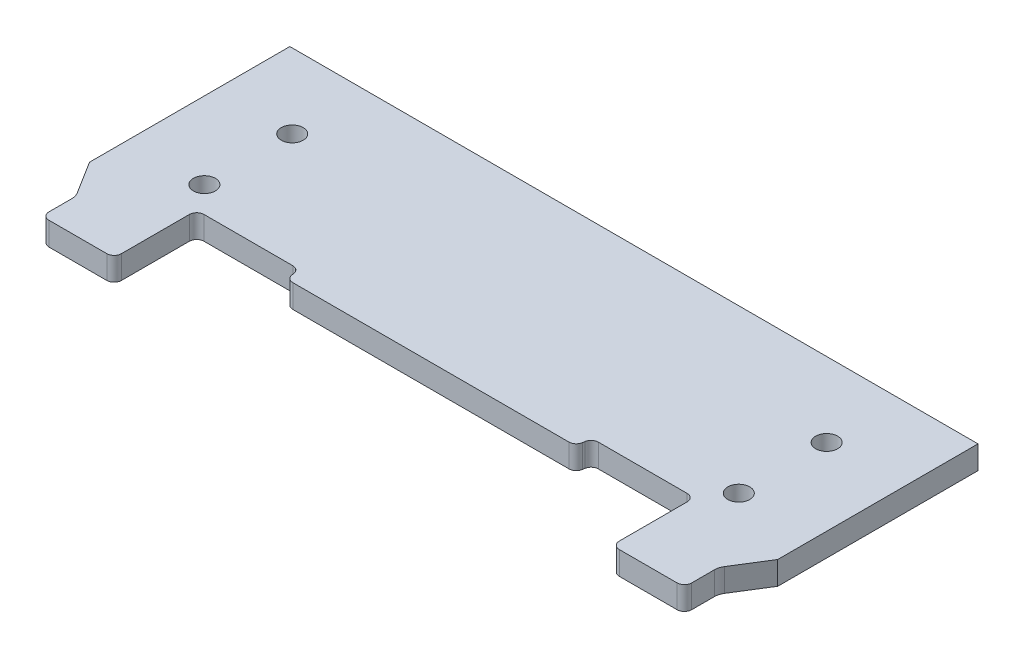
SolidWorks part; units mm, degrees
note: '?' marks a value the reader was unsure of.
material "6061 Alloy"
ref_plane "Front Plane" through (0, 0, 0) normal (0, 0, 1) x (1, 0, 0)
ref_plane "Top Plane" through (0, 0, 0) normal (0, 1, 0) x (1, 0, 0)
ref_plane "Right Plane" through (0, 0, 0) normal (1, 0, 0) x (0, 0, -1)
sketch "Sketch1" plane through (0, 0, 0) normal (0, 1, 0) x (1, 0, 0)
  line L0 (0, 0) -> (0, -55.55) construction
  line L1 (-83.4462, -16.178) -> (-71.2857, -8.5793) construction
  line L6 (0, 0) -> (-59.046, 61.1439) construction
  line L7 (0, 0) -> (-72.0841, -45.0431) construction
  line L8 (-33.174, 78.2591) -> (-23.2129, 67.9442) construction
  line L9 (-72.0841, -45.0431) -> (-70.388, -43.9833) construction
  line L10 (-70.388, -43.9833) -> (-84.9608, -20.662) construction
  line L11 (-84.9608, -20.662) -> (-72.2401, -12.7132) construction
  line L12 (-72.2401, -12.7132) -> (-43.0945, -59.3558) construction
  line L13 (-43.0945, -59.3558) -> (-55.8152, -67.3046) construction
  line L14 (-55.8152, -67.3046) -> (-70.388, -43.9833) construction
  line L21 (-59.046, 61.1439) -> (-57.6566, 59.7052)
  line L22 (-77.4385, 40.6021) -> (-37.8748, 78.8083) construction
  line L23 (-73.9694, 32.6911) -> (-77.0537, 35.885)
  line L24 (-37.8748, 78.8083) -> (-27.4549, 68.0182) construction
  line L25 (-27.4549, 68.0182) -> (-67.0186, 29.812) construction
  line L26 (-67.0186, 29.812) -> (-77.4385, 40.6021) construction
  line L27 (-43.0945, -64.8266) -> (-34, -64.8266)
  line L33 (-86.5505, -18.1178) -> (-71.2857, -8.5793) construction
  line L34 (0, 0) -> (0, 50000) construction
  line L35 (0, 0) -> (-50000, 0) construction
  line L36 (-64.3366, -55.55) -> (-19.7189, -55.55) construction
  line L38 (-67.0927, 25.57) -> (-79.5965, 38.5181) construction
  line L39 (-54.9774, -64.8266) -> (0, -64.8266) construction
  line L40 (-35.7168, 80.8923) -> (-23.2129, 67.9442) construction
  line L41 (-38.9606, -60.3102) -> (-54.2255, -69.8488) construction
  line L42 (-34, -55.55) -> (-19.7189, -55.55) construction
  line L43 (-43.0945, -64.8266) -> (-43.0945, -58.4123) construction
  line L45 (73.9694, 32.6911) -> (77.0537, 35.885)
  line L46 (-71.2857, -8.5793) -> (-38.9606, -60.3102) construction
  line L47 (83.4462, -16.178) -> (79.6809, -13.8252)
  line L48 (69.4846, -16.1792) -> (43.8945, -57.132)
  line L50 (43.0945, -64.8266) -> (34, -64.8266)
  line L51 (34, -55.55) -> (34, -64.8266)
  line L52 (0, 0) -> (72.0841, -45.0431) construction
  line L53 (0, 0) -> (59.046, 61.1439) construction
  line L54 (-30.0897, 75.0653) -> (-30.2847, 63.8954)
  line L55 (-62.7996, 32.4961) -> (-30.2847, 63.8954)
  line L56 (-30.0897, 75.0653) -> (-33.174, 78.2591)
  line L57 (73.9694, 32.6911) -> (77.0537, 35.885)
  line L58 (30.0897, 75.0653) -> (33.174, 78.2591)
  line L59 (-34, -55.55) -> (-34, -53.55)
  line L60 (62.7996, 32.4961) -> (30.2847, 63.8954)
  line L61 (-73.9694, 32.6911) -> (-62.7996, 32.4961)
  line L62 (-77.0537, 35.885) -> (-67.0927, 25.57) construction
  line L63 (-83.4462, -16.178) -> (-79.6809, -13.8252)
  line L64 (-79.6809, -13.8252) -> (-69.4846, -16.1792)
  line L65 (-69.4846, -16.1792) -> (-43.8945, -57.132)
  line L66 (-27.4549, 68.0182) -> (-23.2129, 67.9442) construction
  line L67 (-72.2401, -12.7132) -> (-71.2857, -8.5793) construction
  line L68 (30.0897, 75.0653) -> (30.2847, 63.8954)
  line L69 (73.9694, 32.6911) -> (62.7996, 32.4961)
  line L70 (-34, -55.55) -> (-34, -64.8266)
  line L71 (79.6809, -13.8252) -> (69.4846, -16.1792)
  line L72 (-34, -53.55) -> (-20, -53.55)
  line L73 (-20, -53.55) -> (-19.7189, -55.55)
  line L74 (-19.7189, -55.55) -> (19.7189, -55.55)
  line L75 (20, -53.55) -> (19.7189, -55.55)
  line L76 (34, -53.55) -> (20, -53.55)
  line L77 (34, -55.55) -> (34, -53.55)
  line L78 (-43.0945, -64.8266) -> (-43.8945, -64.8266)
  line L79 (-19.7189, -55.55) -> (0, -55.55) construction
  line L80 (-19.7189, -55.55) -> (34, -55.55) construction
  line L81 (-43.8945, -64.8266) -> (-43.8945, -57.132)
  line L82 (-43.0945, -58.4123) -> (-43.8945, -57.132) construction
  line L83 (43.8945, -64.8266) -> (43.8945, -57.132)
  line L84 (43.0945, -64.8266) -> (43.8945, -64.8266)
  line L97 (-23.2129, 67.9442) -> (-67.0927, 25.57) construction
  circle A0 centre (0, 0) radius 85 construction
  circle A1 centre (0, 0) radius 90 construction
  arc A51 (-77.0537, 35.885) -> (-83.4462, -16.178) centre (0, 0) ccw
  arc A52 (77.0537, 35.885) -> (83.4462, -16.178) centre (0, 0) cw
  arc A54 (-33.174, 78.2591) -> (33.174, 78.2591) centre (0, 0) cw
  point P29 (-31.6318, 76.6622)
  point P33 (-47.2368, 48.9151)
  point P34 (31.6318, 76.6622)
  point P35 (-57.6673, -36.0345)
  point P85 (-57.6566, 59.7052)
  dimension "D2" = 58
  dimension "D10" = 82
  dimension "D12" = 170
  dimension "D14" = 34
  dimension "D13" = 2
  dimension "D15" = 3
  dimension "D3" = 180
  dimension "D4" = 64.8266
  dimension "D5" = 44
  dimension "D6" = 15
  dimension "D7" = 55
  dimension "D8" = 55.55
  dimension "D9" = 2
  dimension "D11" = 2
  dimension "D16" = 7
  dimension "D17" = 7
  dimension "D18" = 0.5
  dimension "D19" = 1
  dimension "D20" = 14
  dimension "D21" = 0.8
extrude "Boss-Extrude4" add sketch "Sketch1" along normal mid plane 3.175
ref_point "Rear_Axle_Center (L)"
ref_axis "Rear_Axle_Proj (L)" through (46.5421, 0, -48.1958) along (0, 1, 0)?
ref_point "Front_Axle_Center (L)"
ref_axis "Front_Axle_Proj (L)" through (57.2432, 0, 35.7696) along (0, 1, 0)?
ref_point "Front_Axle_Center (R)"
ref_axis "Front_Axle_Proj (R)" through (-57.2432, 0, 35.7696) along (0, 1, 0)?
ref_point "Read_Axle_Center (R)"
ref_axis "Rear_Axle_Proj (R)" through (-46.5421, 0, -48.1958) along (0, 1, 0)?
sketch "Sketch17" plane through (0, 1.5875, 0) normal (0, 1, 0) x (1, 0, 0)
  line L0 (0, -50.55) -> (0, -55.55) construction
  line L1 (-19.7189, -55.55) -> (19.7189, -55.55) construction
  circle A0 centre (0, -50.55) radius 8.5
  dimension "D1" = 17
  dimension "D2" = 5
extrude "Boss-Extrude5" [suppressed] add sketch "Sketch17" against normal up to surface (3.175 mm away)
ref_plane "Plane1" through (0, 0, 10) normal (0, 0, 1) x (1, 0, 0)
hole_wizard "M3 Clearance Hole3" positions "Sketch18" profile "Sketch19" hole size "M3" standard "ANSI Metric" end condition through all
sketch "Sketch18" plane through (0, -1.5875, 0) normal (0, -1, 0) x (-1, 0, 0)
  line L0 (-36.5, -50) -> (-36.5, -38) construction
  line L3 (0, 0) -> (0, -38) construction
  line L4 (36.5, -50) -> (36.5, -38) construction
  line L6 (0, -38) -> (36.5, -38) construction
  line L8 (0, -38) -> (-36.5, -38) construction
  line L9 (-36.5, -44) -> (36.5, -44) construction
  line L10 (0, -44) -> (0, 0) construction
  point P1 (36.5, -50)
  point P3 (36.5, -38)
  point P5 (-36.5, -50)
  point P33 (-36.5, -38)
  dimension "D1" = 12
  dimension "D2" = 73
  dimension "D4" = 38
sketch "Sketch19" plane through (-36.5, -1.5875, 50) normal (1, 0, 0) x (0, 0, -1)
  line L0 (0, 0) -> (0, 3.175)
  line L1 (0, 3.175) -> (1.5, 3.175)
  line L2 (1.5, 3.175) -> (1.5, 0)
  line L5 (1.5, 0) -> (0, 0)
  line L11 (0, -6.35) -> (0, 107.95) construction
  dimension "Thru Hole Dia." = 3
  dimension "Thru Hole Depth" = 3.175
hole_wizard "M3 Clearance Hole1" positions "Sketch11" profile "Sketch12" hole size "M3" standard "ANSI Metric" end condition through all
sketch "Sketch11" plane through (0, 1.5875, 0) normal (0, 1, 0) x (1, 0, 0)
  line L0 (83.4462, -16.178) -> (79.6809, -13.8252) construction
  line L2 (73.9694, 32.6911) -> (77.0537, 35.885) construction
  line L4 (-73.9694, 32.6911) -> (-77.0537, 35.885) construction
  line L6 (0, 0) -> (0, -50000) construction
  line L7 (78.4111, 9.6277) -> (84.3664, 10.3589) construction
  line L10 (74.155, 27.2403) -> (78.5423, -8.4914) construction
  line L12 (78.4111, 9.6277) -> (76.3487, 9.3744) construction
  arc A7 (77.964, -12.7523) -> (72.563, 31.2347) centre (0, 0) ccw construction
  arc A13 (-77.964, -12.7523) -> (-72.563, 31.2347) centre (0, 0) cw construction
  arc A17 (83.4462, -16.178) -> (77.0537, 35.885) centre (0, 0) ccw construction
  point P34 (78.5423, -8.4914)
  point P66 (74.155, 27.2403)
  point P70 (-74.155, 27.2403)
  point P71 (-78.5423, -8.4914)
  dimension "D1" = 6
  dimension "D2" = 36
sketch "Sketch12" plane through (-78.5423, 1.5875, 8.4914) normal (1, 0, 0) x (0, 0, 1)
  line L0 (0, 0) -> (0, 3.175)
  line L1 (0, 3.175) -> (1.55, 3.175)
  line L2 (1.55, 3.175) -> (1.55, 0)
  line L5 (1.55, 0) -> (0, 0)
  line L11 (0, -6.35) -> (0, 107.95) construction
  dimension "Thru Hole Dia." = 3.1
  dimension "Thru Hole Depth" = 3.175
hole_wizard "M3 Clearance Hole4" positions "Sketch9" profile "Sketch10" hole size "M3" standard "ANSI Metric" end condition through all
sketch "Sketch9" plane through (0, -1.5875, 0) normal (0, -1, 0) x (-1, 0, 0)
  line L0 (0, 0) -> (0, 63.4318) construction
  line L1 (-38.0437, 52.9272) -> (38.0437, 52.9272) construction
  line L3 (61.0625, 30.6981) -> (-61.0625, 30.6981) construction
  line L4 (-67.0993, -15.2789) -> (67.0993, -15.2789) construction
  line L5 (50.1419, -42.4164) -> (-50.1419, -42.4164) construction
  line L6 (-61.0625, 30.6981) -> (-38.0437, 52.9272) construction
  line L7 (38.0437, 52.9272) -> (61.0625, 30.6981) construction
  line L8 (67.0993, -15.2789) -> (50.1419, -42.4164) construction
  line L9 (-50.1419, -42.4164) -> (-67.0993, -15.2789) construction
  line L10 (0, 0) -> (-44.8055, 46.3974) construction
  line L11 (0, 0) -> (44.8055, 46.3974) construction
  line L12 (0, 0) -> (-96.9468, 0) construction
  line L14 (-55.1231, -34.4448) -> (0, 0) construction
  line L15 (0, 0) -> (55.1231, -34.4448) construction
  line L18 (-69.4846, -16.1792) -> (-43.8945, -57.132) construction
  line L19 (-62.7996, 32.4961) -> (-30.2847, 63.8954) construction
  point P0 (-67.0993, -15.2789)
  point P2 (-50.1419, -42.4164)
  point P9 (-61.0625, 30.6981)
  point P11 (-38.0437, 52.9272)
  point P30 (50.1419, -42.4164)
  point P31 (67.0993, -15.2789)
  point P32 (38.0437, 52.9272)
  point P33 (61.0625, 30.6981)
  dimension "D9" = 46
  dimension "D10" = 46
  dimension "D11" = 32
  dimension "D12" = 32
  dimension "D7" = 58
  dimension "D5" = 32
  dimension "D6" = 2.5
  dimension "D8" = 9.4
  dimension "D2" = 44
  dimension "D3" = 32
  dimension "D4" = 2.5
  dimension "D13" = 9.4
sketch "Sketch10" plane through (67.0993, -1.5875, 15.2789) normal (1, 0, 0) x (0, 0, -1)
  line L0 (0, 0) -> (0, 3.175)
  line L1 (0, 3.175) -> (1.475, 3.175)
  line L2 (1.475, 3.175) -> (1.475, 0)
  line L5 (1.475, 0) -> (0, 0)
  line L11 (0, -6.35) -> (0, 107.95) construction
  dimension "Thru Hole Dia." = 2.95
  dimension "Thru Hole Depth" = 3.175
hole_wizard "M3 Clearance Hole2" positions "Sketch13" profile "Sketch14" hole size "M3" standard "ANSI Metric" end condition through all
sketch "Sketch13" plane through (0, 1.5875, 0) normal (0, 1, 0) x (1, 0, 0)
  line L0 (0, 0) -> (0, 85) construction
  line L2 (-24, 47) -> (-24, 81) construction
  line L3 (-24, 47) -> (24, 47) construction
  line L4 (-24, 81) -> (24, 81) construction
  line L5 (24, 47) -> (24, 81) construction
  line L6 (-24, 47) -> (24, 81) construction
  line L7 (-24, 81) -> (24, 47) construction
  line L8 (-38.0437, 52.9272) -> (-61.0625, 30.6981) construction
  line L10 (-36.307, 51.1289) -> (-59.3259, 28.8998) construction
  line L11 (-16.3488, 39.8187) -> (-31.6313, 55.6441) construction
  line L12 (-16.3488, 39.8187) -> (-48.7191, 8.559) construction
  line L13 (-31.6313, 55.6441) -> (-64.0016, 24.3845) construction
  line L14 (-48.7191, 8.559) -> (-64.0016, 24.3845) construction
  line L15 (-16.3488, 39.8187) -> (-64.0016, 24.3845) construction
  line L16 (-31.6313, 55.6441) -> (-48.7191, 8.559) construction
  line L17 (-49.5531, 41.8127) -> (-40.1752, 32.1016) construction
  line L18 (-27, 76.4978) -> (-27, 80.5978) construction
  arc A0 (33.174, 78.2591) -> (-33.174, 78.2591) centre (0, 0) ccw construction
  circle A1 centre (-16.2162, 44) radius 3 construction
  circle A2 centre (-27, 76.4978) radius 3 construction
  point P65 (0, 64)
  point P181 (-27, 76.4978)
  point P184 (27, 76.4978)
  dimension "D7" = 6
  dimension "D1" = 48
  dimension "D2" = 34
  dimension "D3" = 4
  dimension "D5" = 45
  dimension "D6" = 22
  dimension "D8" = 4.1
  dimension "D4" = 2.5
sketch "Sketch14" plane through (27, 1.5875, -76.4978) normal (1, 0, 0) x (0, 0, 1)
  line L0 (0, 0) -> (0, 3.175)
  line L1 (0, 3.175) -> (1.55, 3.175)
  line L2 (1.55, 3.175) -> (1.55, 0)
  line L5 (1.55, 0) -> (0, 0)
  line L11 (0, -6.35) -> (0, 107.95) construction
  dimension "Thru Hole Dia." = 3.1
  dimension "Thru Hole Depth" = 3.175
hole_wizard "M3 Clearance Hole5" [suppressed] positions "Sketch24" profile "Sketch25" hole size "M3" standard "ANSI Metric"
sketch "Sketch24" plane through (0, 1.5875, 0) normal (0, 1, 0) x (1, 0, 0)
  line L1 (-11, -4.4) -> (11, -4.4) construction
  line L2 (11, -4.4) -> (11, -36.4) construction
  line L3 (11, -36.4) -> (-11, -36.4) construction
  line L4 (-11, -36.4) -> (-11, -4.4) construction
  line L7 (-11, 37.6) -> (11, 37.6) construction
  line L8 (0, -4.4) -> (0, 0) construction
  line L9 (0, 0) -> (0, 37.6) construction
  point P8 (-11, -4.4)
  point P10 (11, -4.4)
  point P12 (11, -36.4)
  point P14 (-11, -36.4)
  point P42 (-11, 37.6)
  point P45 (11, 37.6)
  dimension "D1" = 22
  dimension "D2" = 32
  dimension "D3" = 4.4
  dimension "D4" = 42
sketch "Sketch25" plane through (-11, 1.5875, 4.4) normal (1, 0, 0) x (0, 0, 1)
  line L0 (0, 0) -> (0, 3.175)
  line L1 (0, 3.175) -> (1.5, 3.175)
  line L2 (1.5, 3.175) -> (1.5, 0)
  line L5 (1.5, 0) -> (0, 0)
  line L11 (0, -6.35) -> (0, 107.95) construction
  dimension "Thru Hole Dia." = 3
  dimension "Thru Hole Depth" = 3.175
sketch "Sketch20" plane through (0, 1.5875, 0) normal (0, 1, 0) x (1, 0, 0)
  line L0 (-16.1485, 44) -> (-16.1485, 39) construction
  line L1 (-14.6485, 44) -> (-14.6485, 39)
  line L2 (-17.6485, 44) -> (-17.6485, 39)
  line L3 (0, 0) -> (0, 85) construction
  line L5 (16.1485, 44) -> (16.1485, 39) construction
  line L6 (14.6485, 44) -> (14.6485, 39)
  line L7 (17.6485, 44) -> (17.6485, 39)
  arc A0 (-14.6485, 44) -> (-17.6485, 44) centre (-16.1485, 44) ccw
  arc A1 (-17.6485, 39) -> (-14.6485, 39) centre (-16.1485, 39) ccw
  arc A5 (33.174, 78.2591) -> (-33.174, 78.2591) centre (0, 0) ccw construction
  arc A7 (14.6485, 44) -> (17.6485, 44) centre (16.1485, 44) cw
  arc A8 (17.6485, 39) -> (14.6485, 39) centre (16.1485, 39) cw
  point P2 (-16.1485, 41.5)
  point P16 (16.1485, 41.5)
  dimension "D1" = 44
  dimension "D2" = 3
  dimension "D3" = 5
  dimension "D4" = 16.1485
extrude "Cut-Extrude1" [suppressed] cut sketch "Sketch20" against normal through all
sketch "Sketch22" plane through (0, 1.5875, 0) normal (0, 1, 0) x (1, 0, 0)
  line L0 (-56.6896, -36.6556) -> (-58.0464, -37.5035) construction
  line L1 (-69.4846, -16.1792) -> (-43.8945, -57.132) construction
  line L3 (30.2452, 66.1578) -> (65.062, 32.5356)
  line L4 (71.6894, -15.6702) -> (43.8945, -60.1514)
  line L5 (-19.7189, -55.55) -> (19.7189, -55.55) construction
  line L6 (-43.8945, -64.8266) -> (-43.8945, -57.132) construction
  line L28 (-30.2452, 66.1578) -> (-65.062, 32.5356)
  line L29 (-71.6894, -15.6702) -> (-43.8945, -60.1514)
  line L30 (-79.6809, -13.8252) -> (-69.4846, -16.1792) construction
  line L31 (0, 85) -> (0, -55.55) construction
  line L32 (-46.5421, 48.1958) -> (-47.6536, 49.3467) construction
  line L37 (-20, -53.55) -> (-19.7189, -55.55)
  line L38 (-20, -53.55) -> (-19.7189, -55.55)
  line L40 (-43.8945, -57.132) -> (-43.8945, -64.8266)
  line L41 (-43.8945, -57.132) -> (-43.8945, -64.8266)
  line L43 (43.8945, -64.8266) -> (43.8945, -57.132)
  line L44 (43.8945, -64.8266) -> (43.8945, -57.132)
  line L56 (-19.7189, -55.55) -> (19.7189, -55.55)
  line L58 (19.7189, -55.55) -> (20, -53.55)
  line L59 (20, -53.55) -> (34, -53.55)
  line L60 (34, -53.55) -> (34, -64.8266)
  line L61 (34, -64.8266) -> (43.8945, -64.8266)
  line L63 (43.8945, -57.132) -> (69.4846, -16.1792)
  line L64 (69.4846, -16.1792) -> (79.6809, -13.8252)
  line L65 (79.6809, -13.8252) -> (83.4462, -16.178)
  line L66 (77.0537, 35.885) -> (73.9694, 32.6911)
  line L67 (73.9694, 32.6911) -> (62.7996, 32.4961)
  line L68 (62.7996, 32.4961) -> (30.2847, 63.8954)
  line L69 (30.2847, 63.8954) -> (30.0897, 75.0653)
  line L70 (30.0897, 75.0653) -> (33.174, 78.2591)
  line L71 (-33.174, 78.2591) -> (-30.0897, 75.0653)
  line L72 (-30.0897, 75.0653) -> (-30.2847, 63.8954)
  line L73 (-30.2847, 63.8954) -> (-62.7996, 32.4961)
  line L74 (-62.7996, 32.4961) -> (-73.9694, 32.6911)
  line L75 (-73.9694, 32.6911) -> (-77.0537, 35.885)
  line L76 (-83.4462, -16.178) -> (-79.6809, -13.8252)
  line L77 (-79.6809, -13.8252) -> (-69.4846, -16.1792)
  line L78 (-69.4846, -16.1792) -> (-43.8945, -57.132)
  line L80 (-43.8945, -64.8266) -> (-34, -64.8266)
  line L81 (-34, -64.8266) -> (-34, -53.55)
  line L82 (-34, -53.55) -> (-20, -53.55)
  line L84 (-19.7189, -55.55) -> (19.7189, -55.55)
  line L86 (19.7189, -55.55) -> (20, -53.55)
  line L87 (20, -53.55) -> (34, -53.55)
  line L88 (34, -53.55) -> (34, -64.8266)
  line L89 (34, -64.8266) -> (43.8945, -64.8266)
  line L91 (43.8945, -57.132) -> (69.4846, -16.1792)
  line L92 (69.4846, -16.1792) -> (79.6809, -13.8252)
  line L93 (79.6809, -13.8252) -> (83.4462, -16.178)
  line L94 (77.0537, 35.885) -> (73.9694, 32.6911)
  line L95 (73.9694, 32.6911) -> (62.7996, 32.4961)
  line L96 (62.7996, 32.4961) -> (30.2847, 63.8954)
  line L97 (30.2847, 63.8954) -> (30.0897, 75.0653)
  line L98 (30.0897, 75.0653) -> (33.174, 78.2591)
  line L99 (-33.174, 78.2591) -> (-30.0897, 75.0653)
  line L100 (-30.0897, 75.0653) -> (-30.2847, 63.8954)
  line L101 (-30.2847, 63.8954) -> (-62.7996, 32.4961)
  line L102 (-62.7996, 32.4961) -> (-73.9694, 32.6911)
  line L103 (-73.9694, 32.6911) -> (-77.0537, 35.885)
  line L104 (-83.4462, -16.178) -> (-79.6809, -13.8252)
  line L105 (-79.6809, -13.8252) -> (-69.4846, -16.1792)
  line L106 (-69.4846, -16.1792) -> (-43.8945, -57.132)
  line L108 (-43.8945, -64.8266) -> (-34, -64.8266)
  line L109 (-34, -64.8266) -> (-34, -53.55)
  line L110 (-34, -53.55) -> (-20, -53.55)
  arc A9 (83.4462, -16.178) -> (77.0537, 35.885) centre (0, 0) ccw
  arc A10 (33.174, 78.2591) -> (-33.174, 78.2591) centre (0, 0) ccw
  arc A11 (-77.0537, 35.885) -> (-83.4462, -16.178) centre (0, 0) ccw
  arc A13 (83.4462, -16.178) -> (77.0537, 35.885) centre (0, 0) ccw
  arc A14 (33.174, 78.2591) -> (-33.174, 78.2591) centre (0, 0) ccw
  arc A15 (-77.0537, 35.885) -> (-83.4462, -16.178) centre (0, 0) ccw
  dimension "D2" = 1.6
  dimension "D1" = 0
extrude "Boss-Extrude6" add sketch "Sketch22" against normal up to surface (3.175 mm away) up to face at (-27, -1.5875, -74.9478)
fillet "Fillet1" radius 2 14 edges at (-30.0897, 0, -75.0653) (30.0897, 0, -75.0653) (-79.6809, 0, 13.8252) (79.6809, 0, 13.8252) (73.9694, 0, -32.6911) (-73.9694, 0, -32.6911) (65.062, 0, -32.5356) (30.2452, 0, -66.1578) (71.6894, 0, 15.6702) (-71.6894, 0, 15.6702) (-65.062, 0, -32.5356) (-30.2452, 0, -66.1578) (43.8945, 0, 60.1514) (-43.8945, 0, 60.1514)
fillet "Fillet3" radius 1 16 edges at (-77.0537, 0, -35.885) (77.0537, 0, -35.885) (83.4462, 0, 16.178) (34, 0, 64.8266) (-34, 0, 64.8266) (-33.174, 0, -78.2591) (33.174, 0, -78.2591) (-83.4462, 0, 16.178) (20, 0, 53.55) (34, 0, 53.55) (-34, 0, 53.55) (-20, 0, 53.55) (19.7189, 0, 55.55) (-19.7189, 0, 55.55) (-43.8945, 0, 64.8266) (43.8945, 0, 64.8266)
sketch "Sketch23" [suppressed] plane through (0, 3.175, 0) normal (0, 1, 0) x (1, 0, 0)
  circle A0 centre (0, -53.55) radius 4.95
  dimension "D1" = 9.9
extrude "Cut-Extrude2" [suppressed] cut sketch "Sketch23" against normal through all
sketch "Sketch26" [suppressed] plane through (0, 3.175, 0) normal (0, 1, 0) x (1, 0, 0)
  line L0 (0, 0) -> (0, 50) construction
  line L1 (-92.5, 5) -> (92.5, 5)
  line L2 (-92.5, 5) -> (-92.5, 95)
  line L3 (-92.5, 95) -> (92.5, 95)
  line L4 (92.5, 5) -> (92.5, 95)
  line L5 (-92.5, 5) -> (92.5, 95) construction
  line L6 (-92.5, 95) -> (92.5, 5) construction
  point P0 (0, 50)
  dimension "D1" = 90
  dimension "D2" = 185
  dimension "D3" = 5
extrude "Cut-Extrude3" [suppressed] cut sketch "Sketch26" against normal through all
fillet "Fillet4" [suppressed] radius 5
sketch "Sketch27" plane through (0, 1.5875, 0) normal (0, 1, 0) x (1, 0, 0)
  line L0 (-18.8496, -55.55) -> (18.8496, -55.55) construction
  line L1 (-47, -67.8266) -> (47, -67.8266)
  line L2 (-47, -67.8266) -> (-47, -27.8266)
  line L3 (-47, -27.8266) -> (47, -27.8266)
  line L4 (47, -67.8266) -> (47, -27.8266)
  line L5 (42.8945, -64.8266) -> (35, -64.8266) construction
  point P6 (0, -55.55)
  point P7 (0, -27.8266)
  dimension "D1" = 94
  dimension "D2" = 40
  dimension "D3" = 3
extrude "Cut-Extrude4" cut sketch "Sketch27" against normal through all both and the other way through all flip side to cut
equation "\"D3@Sketch9\"=\"D5@Sketch9\""
equation "\"D4@Sketch9\"=\"D6@Sketch9\""
equation "\"D13@Sketch9\"=\"D8@Sketch9\""
